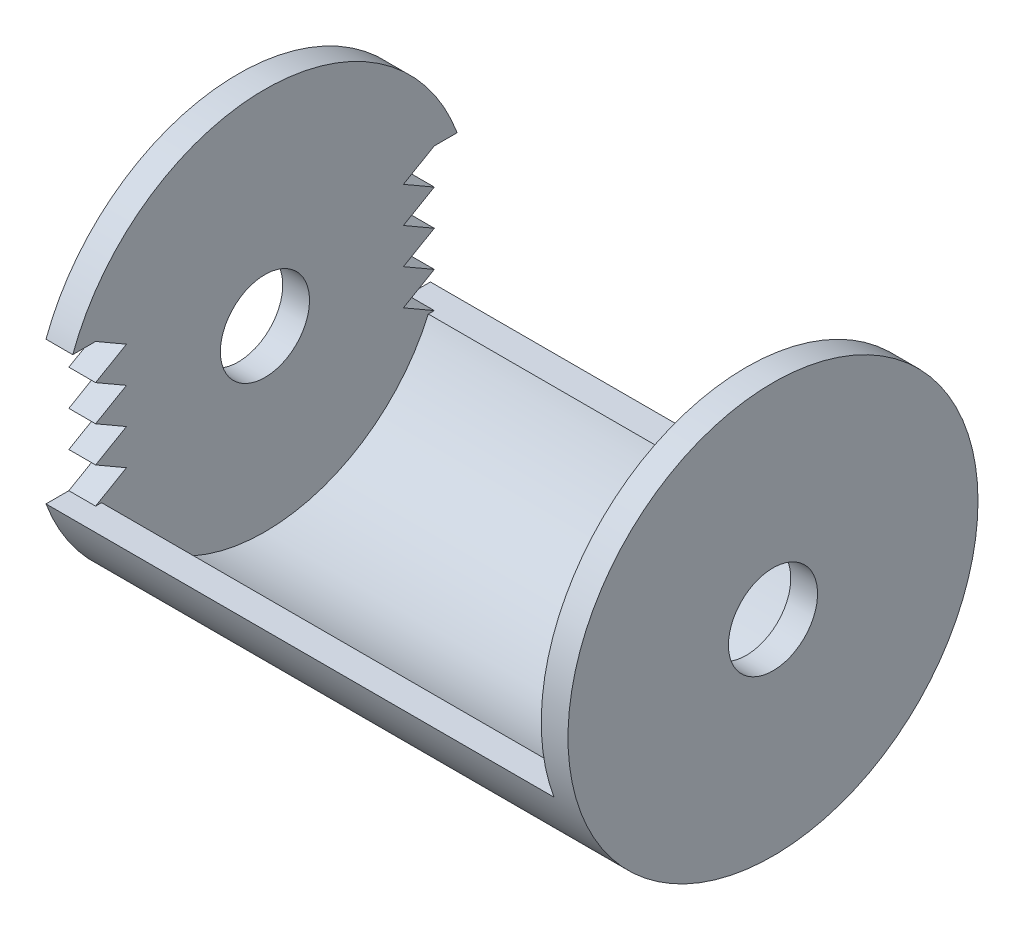
SolidWorks part; units mm, degrees
ref_plane "Front Plane" through (0, 0, 0) normal (0, 0, 1) x (1, 0, 0)
ref_plane "Top Plane" through (0, 0, 0) normal (0, 1, 0) x (1, 0, 0)
ref_plane "Right Plane" through (0, 0, 0) normal (1, 0, 0) x (0, 0, -1)
sketch "Sketch3" plane through (0, 0, 0) normal (1, 0, 0) x (0, 0, -1)
  circle A0 centre (0, 0) radius 29.21
  circle A1 centre (0, 0) radius 6.35
  dimension "D1" = 58.42
  dimension "D2" = 12.7
extrude "Boss-Extrude1" add sketch "Sketch3" along normal blind 76.2
sketch "Sketch4" plane through (0, 0, 0) normal (0, 0, 1) x (1, 0, 0)
  line L0 (76.2, 29.21) -> (0, 29.21) construction
  line L1 (3.81, 68.58) -> (72.39, 68.58)
  line L2 (3.81, 68.58) -> (3.81, -10.16)
  line L3 (3.81, -10.16) -> (72.39, -10.16)
  line L4 (72.39, 68.58) -> (72.39, -10.16)
  line L5 (3.81, 68.58) -> (72.39, -10.16) construction
  line L6 (3.81, -10.16) -> (72.39, 68.58) construction
  point P0 (38.1, 29.21)
  dimension "D1" = 78.74
  dimension "D2" = 68.58
extrude "Cut-Extrude1" cut sketch "Sketch4" against normal through all both and the other way through all
shell "Shell4" thickness 3.81 removed face at (38.1, -10.16, 0)
sketch "Sketch5" plane through (0, 0, 0) normal (-1, 0, 0) x (0, 0, 1)
  line L0 (0, 29.21) -> (0, -29.21) construction
  line L1 (24.13, 10.16) -> (19.7306, 7.62)
  line L2 (19.7306, 7.62) -> (24.13, 5.08)
  line L3 (24.13, 5.08) -> (19.7306, 2.54)
  line L4 (19.7306, 2.54) -> (24.13, 0)
  line L5 (24.13, 0) -> (19.7306, -2.54)
  line L6 (19.7306, -2.54) -> (24.13, -5.08)
  line L7 (24.13, -5.08) -> (19.7306, -7.62)
  line L8 (19.7306, -7.62) -> (24.13, -10.16)
  line L9 (24.13, -10.16) -> (29.21, -10.16)
  line L10 (29.21, -10.16) -> (29.21, 10.16)
  line L11 (29.21, 10.16) -> (24.13, 10.16)
  line L12 (-29.21, 0) -> (29.21, 0) construction
  line L13 (-29.21, 10.16) -> (-24.13, 10.16)
  line L14 (-29.21, -10.16) -> (-29.21, 10.16)
  line L15 (-24.13, -10.16) -> (-29.21, -10.16)
  line L16 (-19.7306, -7.62) -> (-24.13, -10.16)
  line L17 (-24.13, -5.08) -> (-19.7306, -7.62)
  line L18 (-19.7306, -2.54) -> (-24.13, -5.08)
  line L19 (-24.13, 0) -> (-19.7306, -2.54)
  line L20 (-19.7306, 2.54) -> (-24.13, 0)
  line L21 (-24.13, 5.08) -> (-19.7306, 2.54)
  line L22 (-19.7306, 7.62) -> (-24.13, 5.08)
  line L23 (-24.13, 10.16) -> (-19.7306, 7.62)
  circle A3 centre (0, 0) radius 29.21 construction
  point P2 (0, 0)
  point P3 (0, 0)
  point P7 (29.21, 0)
  dimension "D1" = 5.08
  dimension "D2" = 5.08
  dimension "D3" = 5.08
  dimension "D4" = 5.08
extrude "Cut-Extrude2" cut sketch "Sketch5" against normal blind 3.81
